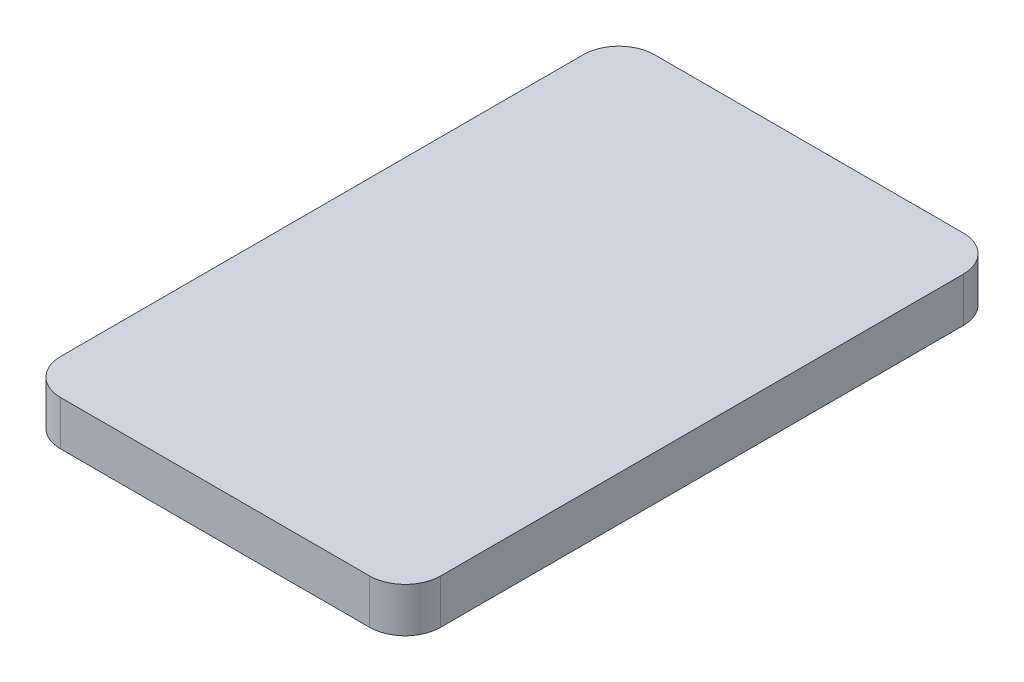
SolidWorks part; units mm, degrees
material "Plain Carbon Steel"
ref_plane "Front Plane" through (0, 0, 0) normal (0, 0, 1) x (1, 0, 0)
ref_plane "Top Plane" through (0, 0, 0) normal (0, 1, 0) x (1, 0, 0)
ref_plane "Right Plane" through (0, 0, 0) normal (1, 0, 0) x (0, 0, -1)
sketch "Sketch1" plane through (0, 0, 0) normal (0, 1, 0) x (1, 0, 0)
  line L0 (0, 0) -> (32, 0)
  line L1 (32, 0) -> (32, 50)
  line L4 (32, 50) -> (0, 50)
  line L7 (0, 50) -> (0, 0)
  dimension "D1" = 50
  dimension "D8" = 32
extrude "Boss-Extrude1" add sketch "Sketch1" along normal blind 3.75
fillet "Fillet1" radius 3 4 edges at (0, 1.875, -50) (32, 1.875, -50) (0, 1.875, 0) (32, 1.875, 0)
